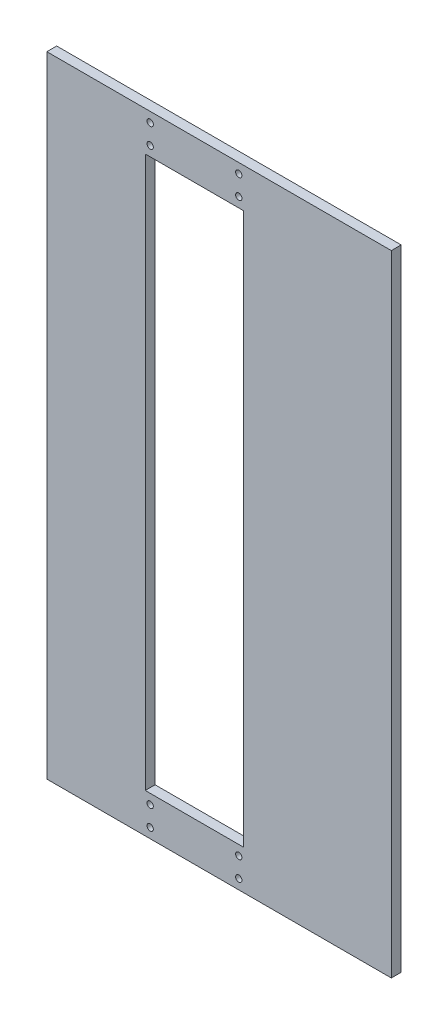
SolidWorks part; units mm, degrees
ref_plane "Front Plane" through (0, 0, 0) normal (0, 0, 1) x (1, 0, 0)
ref_plane "Top Plane" through (0, 0, 0) normal (0, 1, 0) x (1, 0, 0)
ref_plane "Right Plane" through (0, 0, 0) normal (1, 0, 0) x (0, 0, -1)
sketch "Sketch1" plane through (0, 0, 0) normal (0, 0, 1) x (1, 0, 0)
  line L0 (-22.5, 145) -> (-22.5, 155) construction
  line L1 (22.5, -145) -> (-22.5, -145) construction
  line L2 (22.5, -145) -> (22.5, 145) construction
  line L3 (22.5, 145) -> (-22.5, 145) construction
  line L4 (-22.5, -145) -> (-22.5, 145) construction
  line L5 (22.5, -145) -> (-22.5, 145) construction
  line L6 (22.5, 145) -> (-22.5, -145) construction
  line L8 (50, 160) -> (-50, 160)
  line L9 (50, 160) -> (50, -160)
  line L10 (50, -160) -> (-50, -160)
  line L11 (-50, 160) -> (-50, -160)
  line L12 (50, 160) -> (-50, -160) construction
  line L13 (50, -160) -> (-50, 160) construction
  line L14 (25, -140) -> (-25, -140)
  line L15 (25, -140) -> (25, 140)
  line L16 (25, 140) -> (-25, 140)
  line L17 (-25, -140) -> (-25, 140)
  line L18 (25, -140) -> (-25, 140) construction
  line L19 (25, 140) -> (-25, -140) construction
  circle A0 centre (-22.5, 145) radius 1.6
  circle A1 centre (-22.5, 155) radius 1.6
  circle A2 centre (22.5, 145) radius 1.6
  circle A3 centre (22.5, -145) radius 1.6
  circle A4 centre (-22.5, -145) radius 1.6
  circle A8 centre (22.5, 155) radius 1.6
  circle A9 centre (22.5, -155) radius 1.6
  circle A10 centre (-22.5, -155) radius 1.6
  point P0 (0, 0)
  point P9 (0, 0)
  point P26 (0, 0)
  dimension "D4" = 3.2
  dimension "D5" = 3.2
  dimension "D1" = 45
  dimension "D2" = 290
  dimension "D3" = 10
  dimension "D10" = 100
  dimension "D11" = 320
  dimension "D12" = 50
  dimension "D13" = 280
  dimension "D6" = 2
  dimension "D7" = 2
  dimension "D8" = 2
  dimension "D9" = 2
extrude "Boss-Extrude1" add sketch "Sketch1" along normal blind 5
sketch "Sketch2" plane through (0, 0, 0) normal (0, 0, 1) x (1, 0, 0)
  line L1 (50, -160) -> (100, -160)
  line L2 (50, -160) -> (50, 160)
  line L3 (50, 160) -> (100, 160)
  line L4 (100, -160) -> (100, 160)
  dimension "D1" = 50
extrude "Boss-Extrude2" add sketch "Sketch2" along normal blind 5
sketch "Sketch3" plane through (0, 0, 0) normal (0, 0, 1) x (1, 0, 0)
  line L1 (-50, -160) -> (-75, -160)
  line L2 (-50, -160) -> (-50, 160)
  line L3 (-50, 160) -> (-75, 160)
  line L4 (-75, -160) -> (-75, 160)
  dimension "D1" = 25
  dimension "D2" = 320
extrude "Boss-Extrude3" add sketch "Sketch3" along normal blind 5
